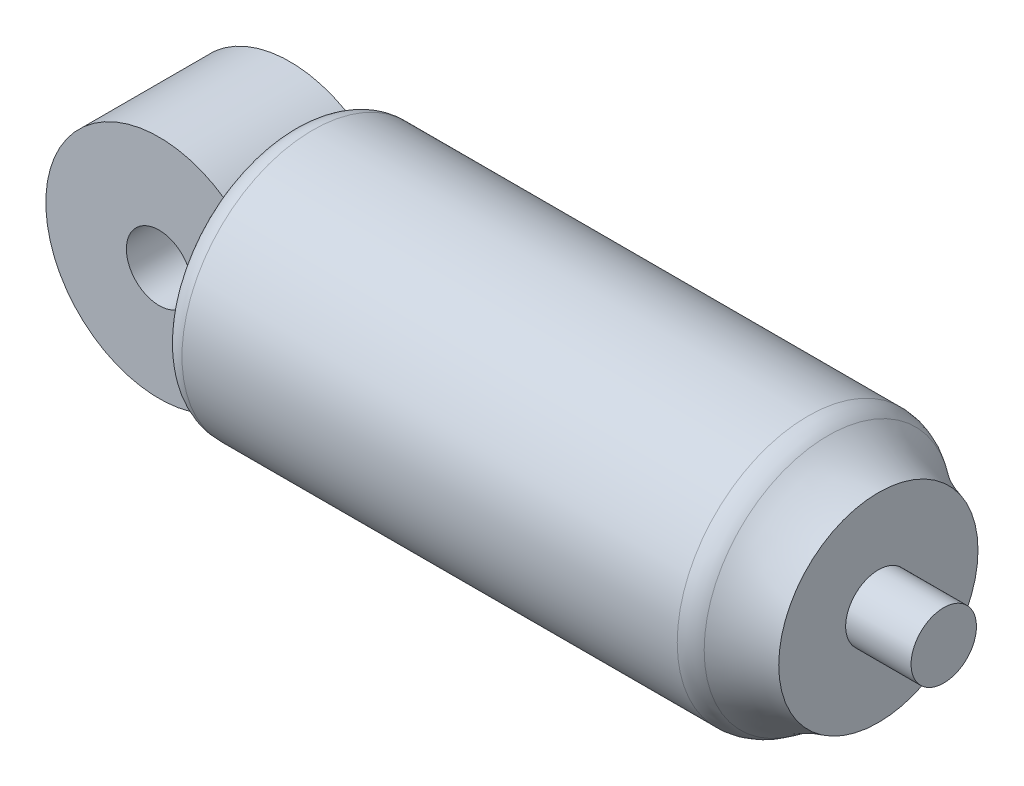
SolidWorks part; units mm, degrees
ref_plane "Front Plane" through (0, 0, 0) normal (0, 0, 1) x (1, 0, 0)
ref_plane "Top Plane" through (0, 0, 0) normal (0, 1, 0) x (1, 0, 0)
ref_plane "Right Plane" through (0, 0, 0) normal (1, 0, 0) x (0, 0, -1)
sketch "Sketch1" plane through (0, 0, 0) normal (0, 0, 1) x (1, 0, 0)
  circle A0 centre (0, 0) radius 34.64
extrude "Boss-Extrude1" add sketch "Sketch1" along normal blind 40
sketch "Sketch2" plane through (0, 0, 0) normal (0, 0, 1) x (1, 0, 0)
  circle A0 centre (0, 0) radius 10
extrude "Cut-Extrude2" cut sketch "Sketch2" along normal through all
sketch "Sketch3" plane through (0, 0, 0) normal (0, 1, 0) x (1, 0, 0)
  line L0 (34.64, -20) -> (154.4314, -20) construction
ref_plane "Plane1" through (40, 0, 0) normal (1, 0, 0) x (0, 0, -1)
sketch "Sketch4" plane through (40, 0, 0) normal (1, 0, 0) x (0, 0, -1)
  line L0 (0, 0) -> (-40, 0) construction
  line L1 (-40, 34.64) -> (-40, -34.64) construction
  circle A0 centre (-20, 0) radius 40
extrude "Boss-Extrude2" add sketch "Sketch4" along normal blind 160 and the other way blind 20
sketch "Sketch5" plane through (20, 0, 0) normal (-1, 0, 0) x (0, 0, 1)
  line L0 (40, -28.283) -> (0, -28.283) construction
  line L1 (0, 28.283) -> (40, 28.283)
  line L2 (0, 28.283) -> (0, -28.283)
  line L3 (0, -28.283) -> (40, -28.283)
  line L4 (40, 28.283) -> (40, -28.283)
extrude "Cut-Extrude3" cut sketch "Sketch5" against normal blind 20
sketch "Sketch6" plane through (0, 0, 0) normal (0, 1, 0) x (1, 0, 0)
  line L0 (200, 20) -> (20, 20) construction
  line L1 (200, -60) -> (200, 20) construction
  line L2 (200, -20) -> (107.6177, -20) construction
  line L4 (-199965.36, -20) -> (200154.4314, -20) construction
  line L5 (182.1244, 20) -> (200, 20)
  line L6 (200, 20) -> (200, 10.4749)
  arc A0 (182.1244, 20) -> (200, 10.4749) centre (209.5991, 50.0251) ccw
revolve "Cut-Revolve1" cut sketch "Sketch6" angle 360 about L2
fillet "Fillet1" radius 10 1 edges at (182.1244, 0, -20)
fillet "Fillet2" radius 7 1 edges at (20, 0, -20)
sketch "Sketch7" plane through (200, 0, 0) normal (1, 0, 0) x (0, 0, -1)
  circle A0 centre (-20, 0) radius 10
extrude "Boss-Extrude5" add sketch "Sketch7" along normal blind 20
